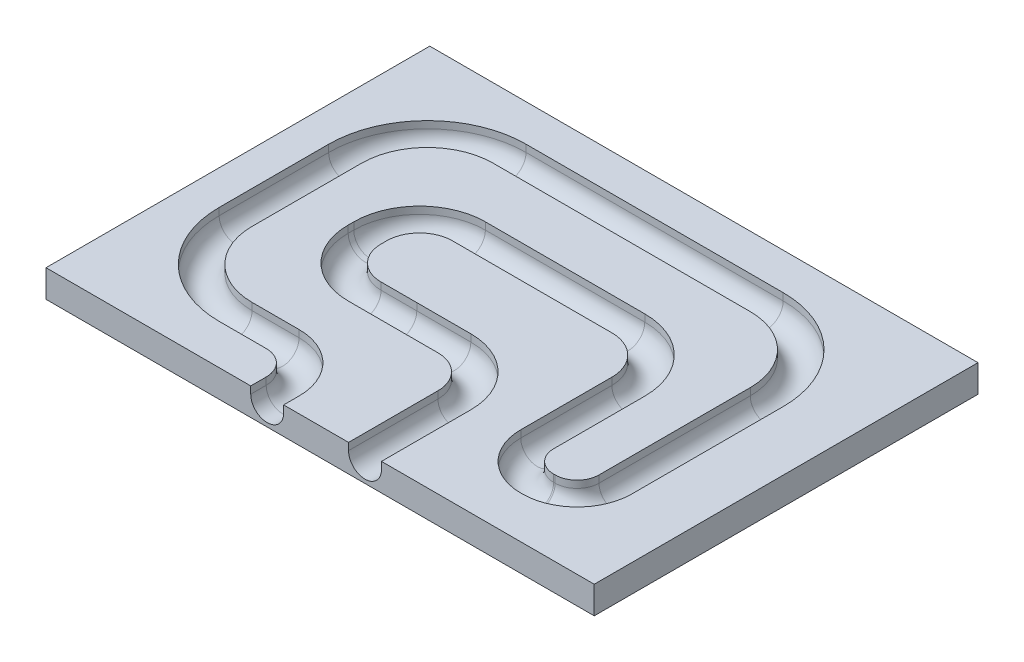
SolidWorks part; units mm, degrees
ref_plane "Front Plane" through (0, 0, 0) normal (0, 0, 1) x (1, 0, 0)
ref_plane "Top Plane" through (0, 0, 0) normal (0, 1, 0) x (1, 0, 0)
ref_plane "Right Plane" through (0, 0, 0) normal (1, 0, 0) x (0, 0, -1)
sketch "Sketch1" plane through (0, 0, 0) normal (0, 1, 0) x (1, 0, 0)
  line L1 (-127, 88.9) -> (127, 88.9)
  line L2 (-127, 88.9) -> (-127, -88.9)
  line L3 (-127, -88.9) -> (127, -88.9)
  line L4 (127, 88.9) -> (127, -88.9)
  line L5 (-127, 88.9) -> (127, -88.9) construction
  line L6 (-127, -88.9) -> (127, 88.9) construction
  point P0 (0, 0)
  dimension "D1" = 254
  dimension "D2" = 177.8
extrude "Boss-Extrude1" add sketch "Sketch1" along normal blind 12.7
sketch "Sketch2" plane through (0, 12.7, 0) normal (0, 1, 0) x (1, 0, 0)
  line L0 (-127, 0) -> (127, 0) construction
  line L1 (-127, 88.9) -> (-127, -88.9) construction
  line L2 (127, -88.9) -> (127, 88.9) construction
  line L3 (0, 88.9) -> (0, -88.9) construction
  line L4 (127, 88.9) -> (-127, 88.9) construction
  line L5 (-127, -88.9) -> (127, -88.9) construction
  line L6 (20.7964, -88.9) -> (20.7964, -47.4887)
  line L7 (-2.0636, -24.6287) -> (-27.1102, -24.6287)
  line L9 (-27.1102, -24.6287) -> (-43.6402, -24.6287)
  line L10 (-66.5002, -1.7687) -> (-66.5002, 0.807)
  line L11 (-43.6402, 23.667) -> (30.2238, 23.667)
  line L12 (55.6238, -1.733) -> (55.6238, -43.941)
  line L13 (73.4038, -61.721) -> (74.0932, -61.721)
  line L14 (91.8732, -43.941) -> (91.8732, 26.1414)
  line L15 (53.7732, 64.2414) -> (-65.3568, 64.2414)
  line L16 (-103.4568, 26.1414) -> (-103.4568, -24.5959)
  line L17 (-65.3568, -62.6959) -> (-43.5748, -62.6959)
  line L18 (-24.5248, -81.7459) -> (-24.5248, -88.9)
  arc A0 (-103.4568, -24.5959) -> (-65.3568, -62.6959) centre (-65.3568, -24.5959) ccw
  arc A1 (91.8732, 26.1414) -> (53.7732, 64.2414) centre (53.7732, 26.1414) ccw
  arc A2 (-65.3568, 64.2414) -> (-103.4568, 26.1414) centre (-65.3568, 26.1414) ccw
  arc A3 (30.2238, 23.667) -> (55.6238, -1.733) centre (30.2238, -1.733) cw
  arc A4 (74.0932, -61.721) -> (91.8732, -43.941) centre (74.0932, -43.941) ccw
  arc A5 (55.6238, -43.941) -> (73.4038, -61.721) centre (73.4038, -43.941) ccw
  arc A6 (20.7964, -47.4887) -> (-2.0636, -24.6287) centre (-2.0636, -47.4887) ccw
  arc A7 (-43.6402, -24.6287) -> (-66.5002, -1.7687) centre (-43.6402, -1.7687) cw
  arc A8 (-66.5002, 0.807) -> (-43.6402, 23.667) centre (-43.6402, 0.807) cw
  arc A9 (-43.5748, -62.6959) -> (-24.5248, -81.7459) centre (-43.5748, -81.7459) cw
  point P26 (0, 0)
  dimension "D1" = 38.1
  dimension "D2" = 25.4
  dimension "D3" = 17.78
  dimension "D4" = 22.86
  dimension "D5" = 19.05
sketch "Sketch3" plane through (0, 0, 88.9) normal (0, 0, 1) x (1, 0, 0)
  line L0 (-24.5248, 12.7) -> (-24.5248, 9.3809) construction
  line L1 (-16.9048, 12.7) -> (-16.9048, 9.3809)
  line L2 (-32.1448, 12.7) -> (-32.1448, 9.3809)
  arc A0 (-16.9048, 12.7) -> (-32.1448, 12.7) centre (-24.5248, 12.7) ccw
  arc A1 (-32.1448, 9.3809) -> (-16.9048, 9.3809) centre (-24.5248, 9.3809) ccw
  point P3 (-24.5248, 11.0405)
  point P8 (-24.5248, 8.6418)
  point P9 (0, 0)
  point P10 (-24.5248, 9.3809)
  dimension "D1" = 7.62
sweep "Cut-Sweep2" cut profiles "Sketch3" path "Sketch2"
sketch "Sketch4" plane through (0, 12.7, 0) normal (0, 1, 0) x (1, 0, 0)
  line L1 (-127, 88.9) -> (127, 88.9)
  line L2 (-127, 88.9) -> (-127, -88.9)
  line L3 (-127, -88.9) -> (127, -88.9)
  line L4 (127, 88.9) -> (127, -88.9)
extrude "Boss-Extrude2" [suppressed] add sketch "Sketch4" along normal blind 2.54
sketch "Sketch6" [suppressed] plane through (0, 0, 88.9) normal (0, 0, 1) x (1, 0, 0)
  line L0 (-24.5248, 12.7) -> (-24.5248, 9.3809) construction
  line L1 (-32.1448, 12.7) -> (-16.9048, 12.7) construction
  line L2 (-43.5748, 9.3809) -> (-16.9048, 9.3809) construction
  line L3 (-16.9048, 12.7) -> (-16.9048, 9.3809)
  line L4 (-32.1448, 12.7) -> (-32.1448, 9.3809)
  line L5 (20.7964, 12.7) -> (20.7964, 9.3809) construction
  line L6 (13.1764, 12.7) -> (28.4164, 12.7) construction
  line L7 (28.4164, 12.7) -> (28.4164, 9.3809)
  line L8 (13.1764, 12.7) -> (13.1764, 9.3809)
  line L9 (-32.1448, 12.7) -> (-16.9048, 12.7)
  line L10 (13.1764, 12.7) -> (28.4164, 12.7)
  arc A0 (-16.9048, 12.7) -> (-32.1448, 12.7) centre (-24.5248, 12.7) ccw
  arc A1 (-32.1448, 9.3809) -> (-16.9048, 9.3809) centre (-24.5248, 9.3809) ccw
  arc A2 (28.4164, 12.7) -> (13.1764, 12.7) centre (20.7964, 12.7) ccw
  arc A3 (13.1764, 9.3809) -> (28.4164, 9.3809) centre (20.7964, 9.3809) ccw
  point P6 (-24.5248, 11.0405)
  point P11 (20.7964, 11.0405)
  line M1 (13.1764, 9.3809) -> (13.1764, 12.7)
  line M2 (13.1764, 12.7) -> (28.4164, 12.7)
  line M3 (28.4164, 12.7) -> (28.4164, 9.3809)
  arc M4 (28.4164, 9.3809) -> (13.1764, 9.3809) centre (20.7964, 9.3809) cw
  line M9 (-32.1448, 12.7) -> (-16.9048, 12.7)
  line M10 (-16.9048, 12.7) -> (-16.9048, 9.3809)
  arc M11 (-16.9048, 9.3809) -> (-32.1448, 9.3809) centre (-24.5248, 9.3809) cw
  line M12 (-32.1448, 9.3809) -> (-32.1448, 12.7)
  dimension "D1" = 7.62
  dimension "D2" = 7.62
extrude "Boss-Extrude4" [suppressed] add sketch "Sketch6" along normal blind 2.54 from offset 1.27 separate body contours M9 M12 M11 M10 | M1 M4 M3 M2 offset against normal yes
